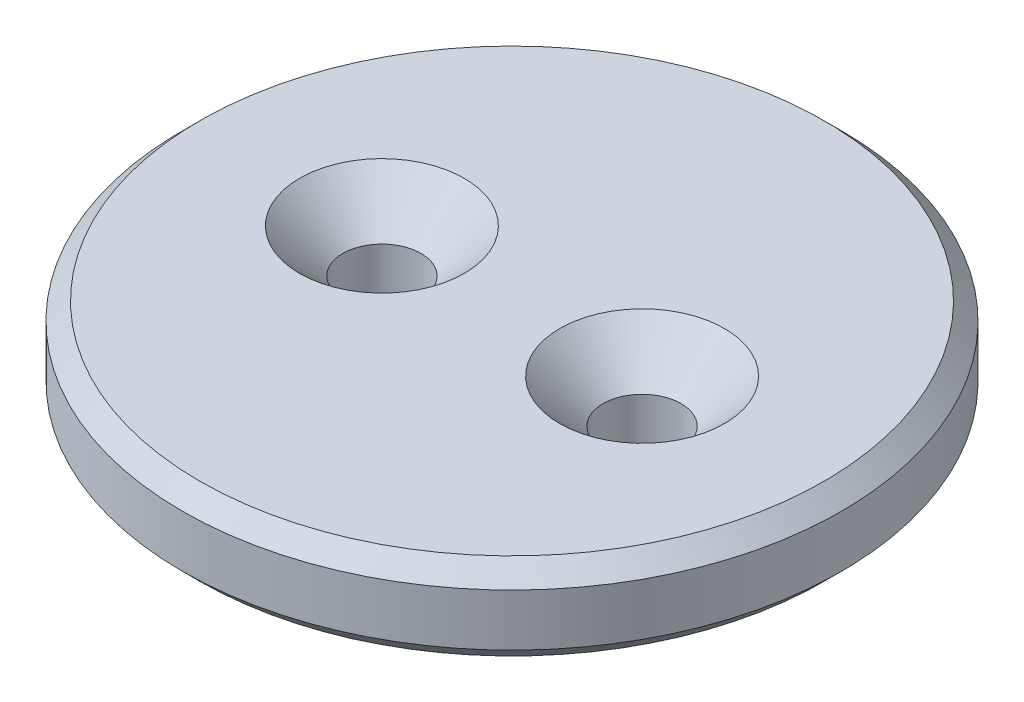
SolidWorks part; units mm, degrees
ref_plane "Front Plane" through (0, 0, 0) normal (0, 0, 1) x (1, 0, 0)
ref_plane "Top Plane" through (0, 0, 0) normal (0, 1, 0) x (1, 0, 0)
ref_plane "Right Plane" through (0, 0, 0) normal (1, 0, 0) x (0, 0, -1)
sketch "Sketch1" plane through (0, 0, 0) normal (0, 1, 0) x (1, 0, 0)
  circle A0 centre (0, 0) radius 19
  dimension "D1" = 38
extrude "Boss-Extrude1" add sketch "Sketch1" along normal blind 5
chamfer "Chamfer2" distance 1 angle 45 2 edges at (0, 0, 19) (0, 5, 19)
sketch "Sketch2" plane through (0, 5, 0) normal (0, 1, 0) x (1, 0, 0)
  line L0 (-19, 0) -> (19, 0) construction
  line L1 (0, 8.9074) -> (0, -6.7104) construction
  circle A0 centre (0, 0) radius 19 construction
  circle A1 centre (-7.5, 0) radius 2.25
  circle A2 centre (7.5, 0) radius 2.25
  dimension "D2" = 4.5
  dimension "D1" = 15
extrude "Cut-Extrude1" cut sketch "Sketch2" against normal through all
chamfer "Chamfer1" distance 2.5 angle 45 2 edges at (7.5, 5, -2.25) (-7.5, 5, 2.25)
sketch "Sketch3" plane through (0, 0, 0) normal (0, -1, 0) x (1, 0, 0)
  line L0 (7.5, 0) -> (-23.4744, 0.191) construction
  line L2 (-12.5, -6.5) -> (12.5, -6.5)
  line L3 (-12.5, -6.5) -> (-12.5, 6.5)
  line L4 (-12.5, 6.5) -> (12.5, 6.5)
  line L5 (12.5, -6.5) -> (12.5, 6.5)
  line L6 (-12.5, -6.5) -> (12.5, 6.5) construction
  line L7 (-12.5, 6.5) -> (12.5, -6.5) construction
  point P3 (0, 0)
  dimension "D1" = 13
  dimension "D2" = 25
extrude "Boss-Extrude2" add sketch "Sketch3" along normal blind 2
sketch "Sketch4" plane through (0, 0, 0) normal (0, 1, 0) x (1, 0, 0)
  circle A0 centre (7.5, 0) radius 2.25 construction
  circle A1 centre (-7.5, 0) radius 2.25 construction
  circle A2 centre (7.5, 0) radius 2.25
  circle A3 centre (-7.5, 0) radius 2.25
extrude "Cut-Extrude2" cut sketch "Sketch4" against normal through all
